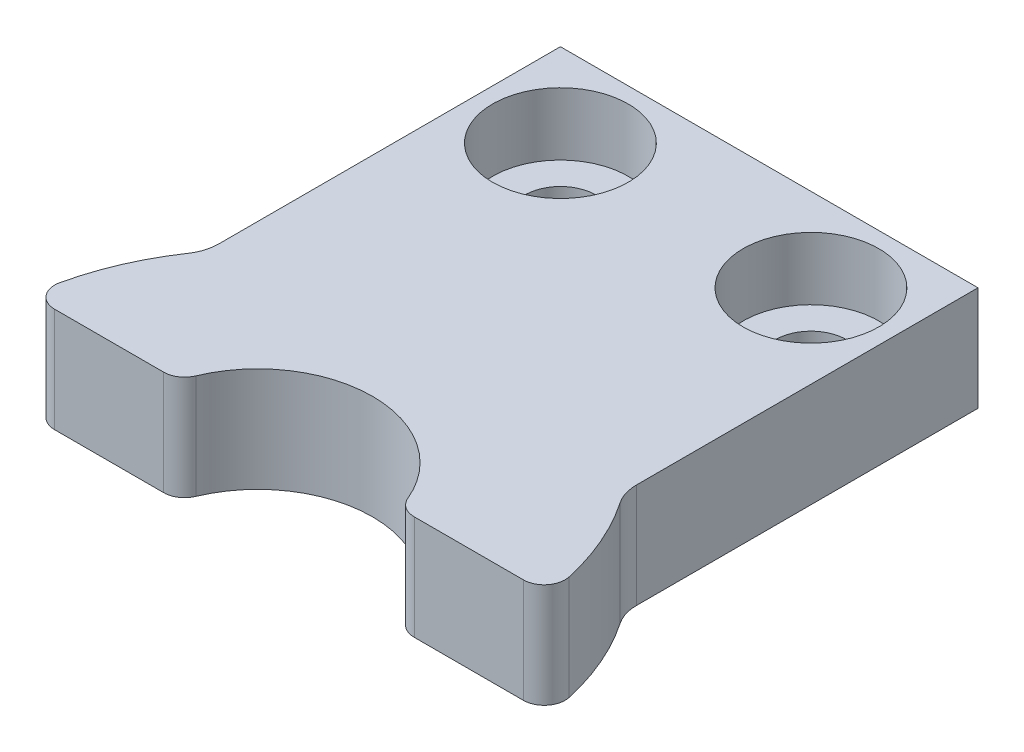
SolidWorks part; units mm, degrees
ref_plane "Front Plane" through (0, 0, 0) normal (0, 0, 1) x (1, 0, 0)
ref_plane "Top Plane" through (0, 0, 0) normal (0, 1, 0) x (1, 0, 0)
ref_plane "Right Plane" through (0, 0, 0) normal (1, 0, 0) x (0, 0, -1)
sketch "Sketch1" plane through (0, 0, 0) normal (0, 1, 0) x (1, 0, 0)
  line L0 (-9, 0) -> (0, 0) construction
  line L1 (0, 0) -> (9, 0) construction
  line L2 (0, 9) -> (0, 0) construction
  arc A0 (9, 0) -> (-9, 0) centre (0, 0) ccw construction
  arc A1 (12.5, 0) -> (-12.5, 0) centre (0, 0) ccw
  arc A2 (5.5, 0) -> (-5.5, 0) centre (0, 0) ccw
  arc A3 (5.5, 0) -> (12.5, 0) centre (9, 0) ccw
  arc A4 (-12.5, 0) -> (-5.5, 0) centre (-9, 0) ccw
  point P4 (0, 9)
  dimension "D2" = 7
  dimension "D1" = 9
extrude "Boss-Extrude1" add sketch "Sketch1" along normal blind 5
sketch "Sketch3" plane through (0, 5, 0) normal (0, 1, 0) x (1, 0, 0)
  line L0 (-10, 7.5) -> (-10, 24.5)
  line L1 (-10, 24.5) -> (10, 24.5)
  line L2 (10, 24.5) -> (10, 7.5)
  line L3 (0, 24.5) -> (0, 0) construction
  arc A0 (12.5, 0) -> (-12.5, 0) centre (0, 0) ccw construction
  arc A1 (10, 7.5) -> (-10, 7.5) centre (0, 0) ccw
  dimension "D1" = 20
  dimension "D2" = 17
extrude "Boss-Extrude2" add sketch "Sketch3" against normal up to surface (5 mm away) up to face at (0, 0, -2.75)
fillet "Fillet1" [suppressed] radius 2
fillet "Fillet2" radius 2 2 edges at (-10, 2.5, -7.5) (10, 2.5, -7.5)
hole_wizard "CBORE for M3 SHCS1" positions "Sketch4" profile "Sketch5" counterbore size "M3" standard "ANSI Metric" end condition through all
sketch "Sketch4" plane through (0, 5, 0) normal (0, 1, 0) x (1, 0, 0)
  line L0 (10, 24.5) -> (-10, 24.5) construction
  line L1 (10, 8.1394) -> (10, 24.5) construction
  line L2 (-10, 24.5) -> (-10, 8.1394) construction
  point P0 (-6, 20.5)
  point P2 (6, 20.5)
  dimension "D1" = 4
  dimension "D2" = 4
  dimension "D3" = 4
sketch "Sketch5" plane through (-6, 5, -20.5) normal (1, 0, 0) x (0, 0, 1)
  line L0 (0, 0) -> (0, 5)
  line L1 (0, 5) -> (1.7, 5)
  line L3 (1.7, 5) -> (1.7, 3)
  line L4 (1.7, 3) -> (3.25, 3)
  line L5 (3.25, 3) -> (3.25, 0)
  line L7 (3.25, 0) -> (0, 0)
  line L11 (0, -6.35) -> (0, 107.95) construction
  dimension "Thru Hole Dia." = 3.4
  dimension "Thru Hole Depth" = 5
  dimension "C'Bore Dia." = 6.5
  dimension "C'Bore Depth" = 3
sketch "Sketch6" plane through (0, 5, 0) normal (0, 1, 0) x (1, 0, 0)
  line L1 (-12.5, 1.5) -> (12.5, 1.5)
  line L2 (-12.5, 1.5) -> (-12.5, -3.5)
  line L3 (-12.5, -3.5) -> (12.5, -3.5)
  line L4 (12.5, 1.5) -> (12.5, -3.5)
  arc A0 (5.5, 0) -> (12.5, 0) centre (9, 0) ccw construction
  arc A1 (-10.3448, 7.0167) -> (-12.5, 0) centre (0, 0) ccw construction
  arc A2 (12.5, 0) -> (10.3448, 7.0167) centre (0, 0) ccw construction
  dimension "D1" = 5
extrude "Cut-Extrude1" cut sketch "Sketch6" against normal through all
fillet "Fillet3" radius 1 4 edges at (12.4097, 2.5, -1.5) (5.2915, 2.5, -1.5) (-5.2915, 2.5, -1.5) (-12.4097, 2.5, -1.5)
other "Move Face1" [suppressed] offset 3 parameters "D1"=3
